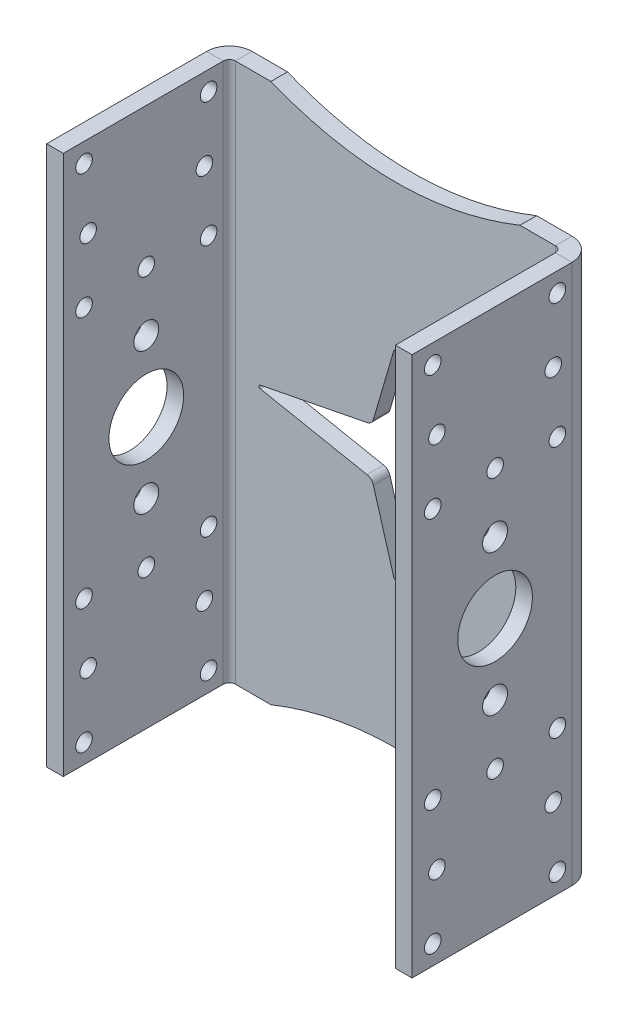
SolidWorks part; units mm, degrees
note: The reader was unsure of these and kept them because the rebuilt part matched: flange length of "边线-法兰1", "边线-法兰2".
ref_plane "前视基准面" through (0, 0, 0) normal (0, 0, 1) x (1, 0, 0)
ref_plane "上视基准面" through (0, 0, 0) normal (0, 1, 0) x (1, 0, 0)
ref_plane "右视基准面" through (0, 0, 0) normal (1, 0, 0) x (0, 0, -1)
sketch "草图1" plane through (0, 0, 0) normal (0, 0, 1) x (1, 0, 0)
  line L1 (-24.9105, 29.2763) -> (19.0895, 29.2763)
  line L2 (-24.9105, 29.2763) -> (-24.9105, -35.7237)
  line L3 (-24.9105, -35.7237) -> (19.0895, -35.7237)
  line L4 (19.0895, 29.2763) -> (19.0895, -35.7237)
  dimension "D1" = 44
  dimension "D2" = 65
base flange "基体-法兰1" sketch "草图1" thickness 2 reverse thickness direction no parameters "D1"=0.7366
edge flange "边线-法兰1" sketch "草图8" flange angle 90 flange length 22 flange position material inside bend radius 0.7366 thickness 2 relief rectangular parameters "D6"=10
sketch "草图8" plane through (-24.9105, 0, 0) normal (-1, 0, 0) x (0, -1, 0)
  line L0 (-29.2763, 0) -> (35.7237, 0) construction
  line L1 (-29.2763, 0) -> (35.7237, 0)
  line L2 (-29.2763, 0) -> (-29.2763, 20)
  line L3 (-29.2763, 20) -> (35.7237, 20)
  line L4 (35.7237, 20) -> (35.7237, 0)
bend "边线折弯1" bend radius 0.7366 bend angle 90 parameters "D5"=1
edge flange "边线-法兰2" sketch "草图11" flange angle 90 flange length 22 flange position material inside bend radius 0.7366 thickness 2 relief rectangular parameters "D6"=10
sketch "草图11" plane through (19.0895, 0, 0) normal (1, 0, 0) x (0, 1, 0)
  line L0 (-35.7237, 0) -> (29.2763, 0) construction
  line L1 (-35.7237, 0) -> (29.2763, 0)
  line L2 (-35.7237, 0) -> (-35.7237, 20)
  line L3 (-35.7237, 20) -> (29.2763, 20)
  line L4 (29.2763, 20) -> (29.2763, 0)
bend "边线折弯2" bend radius 0.7366 bend angle 90 parameters "D5"=2
sketch "草图12" plane through (0, 0, -2) normal (0, 0, -1) x (-1, 0, 0)
  line L16 (-14.3529, -3.2237) -> (0.0821, -0.3953)
  line L17 (2.9105, 9.2763) -> (5.7389, -0.3953)
  line L18 (5.7389, -0.3953) -> (20.1739, -3.2237)
  line L19 (20.1739, -3.2237) -> (5.7389, -6.0522)
  line L20 (5.7389, -6.0522) -> (2.9105, -15.7237)
  line L21 (2.9105, -15.7237) -> (0.0821, -6.0522)
  line L22 (0.0821, -6.0522) -> (-14.3529, -3.2237)
  line L23 (0.0821, -0.3953) -> (2.9105, 9.2763)
extrude "切除-拉伸1" cut sketch "草图12" against normal blind 2 normal cut yes
sketch "草图13" plane through (0, 0, -2) normal (0, 0, -1) x (-1, 0, 0)
  line L0 (2.9105, 29.2763) -> (17.9105, 29.2763)
  line L1 (-16.3529, 29.2763) -> (22.1739, 29.2763) construction
  line L5 (-12.0895, 29.2763) -> (2.9105, 29.2763)
  spline S0 degree 2 poles (-12.0895, 29.2763) (2.9105, 23.2763) (17.9105, 29.2763) knots 0 0 0 1 1 1
extrude "切除-拉伸2" cut sketch "草图13" against normal blind 2 normal cut yes
sketch "草图14" plane through (0, 0, -2) normal (0, 0, -1) x (-1, 0, 0)
  line L0 (2.9105, -35.7237) -> (17.9105, -35.7237)
  line L1 (24.9105, -35.7237) -> (-19.0895, -35.7237) construction
  line L5 (22.1739, -35.7237) -> (-16.3529, -35.7237) construction
  line L6 (-12.0895, -35.7237) -> (2.9105, -35.7237)
  spline S0 degree 2 poles (-12.0895, -35.7237) (2.9105, -29.7237) (17.9105, -35.7237) knots 0 0 0 1 1 1
extrude "切除-拉伸3" cut sketch "草图14" against normal blind 2 normal cut yes
sketch "草图16" plane through (19.0895, 0, 0) normal (1, 0, 0) x (0, 0, -1)
  circle A4 centre (-17.5, 26.9559) radius 1
  circle A5 centre (-2.5, 26.9559) radius 1
  circle A6 centre (-2.5, 11.9559) radius 1
  circle A7 centre (-17.5, 11.9559) radius 1
  circle A9 centre (-3, 19.4559) radius 1
  circle A10 centre (-17, 19.4559) radius 1
  circle A11 centre (-10, 12.4559) radius 1
  circle A12 centre (-10, -18.9034) radius 1
  circle A13 centre (-17, -25.9034) radius 1
  circle A14 centre (-3, -25.9034) radius 1
  circle A15 centre (-17.5, -18.4034) radius 1
  circle A16 centre (-2.5, -18.4034) radius 1
  circle A17 centre (-2.5, -33.4034) radius 1
  circle A18 centre (-17.5, -33.4034) radius 1
  circle A19 centre (-10, -3.2237) radius 4.5
  circle A20 centre (-10, 5.2763) radius 1.5
  circle A21 centre (-10, -11.7237) radius 1.5
extrude "切除-拉伸5" cut sketch "草图16" against normal blind 50 normal cut yes
fillet "圆角2" radius 0.2 1 edges at (-2.9105, 9.2763, -1)
fillet "圆角3" radius 0.2 1 edges at (-20.1739, -3.2237, -1)
fillet "圆角4" radius 0.2 1 edges at (-2.9105, -15.7237, -1)
fillet "圆角5" radius 0.2 1 edges at (14.3529, -3.2237, -1)
fillet "圆角7" radius 1 4 edges at (-5.7389, -6.0522, -1) (-5.7389, -0.3953, -1) (-0.0821, -6.0522, -1) (-0.0821, -0.3953, -1)
sketch "折弯-线1" plane through (0, 0, 0) normal (0, 1, 0) x (1, 0, 0)
sketch "边界框1" plane through (0, 0, 0) normal (0, 1, 0) x (1, 0, 0)
sheet metal parameters "钣金6" thickness 2 parameters "D1"=0.7366
flat pattern "平板型式6" [suppressed]
sketch "折弯-线2" plane through (0, 0, 0) normal (0, 1, 0) x (1, 0, 0)
sketch "边界框2" [suppressed] plane through (0, 0, 0) normal (0, 1, 0) x (1, 0, 0)
sheet metal parameters "钣金7" thickness 2 parameters "D1"=0.7366
flat pattern "平板型式6" [suppressed]
sketch "折弯-线2" plane through (0, 0, 0) normal (0, 1, 0) x (1, 0, 0)
sketch "边界框2" [suppressed] plane through (0, 0, 0) normal (0, 1, 0) x (1, 0, 0)
bend of the flat pattern "展平-<边线折弯1>1"
sheet metal parameters "钣金8" thickness 2 parameters "D1"=0.7366
flat pattern "平板型式6" [suppressed]
sketch "折弯-线2" plane through (0, 0, 0) normal (0, 1, 0) x (1, 0, 0)
sketch "边界框2" [suppressed] plane through (0, 0, 0) normal (0, 1, 0) x (1, 0, 0)
bend of the flat pattern "展平-<边线折弯1>1"
bend of the flat pattern "展平-<边线折弯2>1"
sheet metal parameters "钣金9" thickness 2 parameters "D1"=0.7366
flat pattern "平板型式6" [suppressed]
sketch "折弯-线2" plane through (0, 0, 0) normal (0, 1, 0) x (1, 0, 0)
sketch "边界框2" [suppressed] plane through (0, 0, 0) normal (0, 1, 0) x (1, 0, 0)
bend of the flat pattern "展平-<边线折弯1>1"
bend of the flat pattern "展平-<边线折弯2>1"
sheet metal parameters "钣金10" thickness 2 parameters "D1"=0.7366
flat pattern "平板型式6" [suppressed]
sketch "折弯-线2" plane through (0, 0, 0) normal (0, 1, 0) x (1, 0, 0)
sketch "边界框2" [suppressed] plane through (0, 0, 0) normal (0, 1, 0) x (1, 0, 0)
bend of the flat pattern "展平-<边线折弯1>1"
bend of the flat pattern "展平-<边线折弯2>1"
sheet metal parameters "钣金11" thickness 2 parameters "D1"=0.7366
flat pattern "平板型式6" [suppressed]
sketch "折弯-线2" plane through (0, 0, 0) normal (0, 1, 0) x (1, 0, 0)
sketch "边界框2" [suppressed] plane through (0, 0, 0) normal (0, 1, 0) x (1, 0, 0)
bend of the flat pattern "展平-<边线折弯1>1"
bend of the flat pattern "展平-<边线折弯2>1"
sheet metal parameters "钣金13" thickness 2 parameters "D1"=0.7366
flat pattern "平板型式6" [suppressed]
sketch "折弯-线2" plane through (0, 0, 0) normal (0, 1, 0) x (1, 0, 0)
sketch "边界框2" [suppressed] plane through (0, 0, 0) normal (0, 1, 0) x (1, 0, 0)
bend of the flat pattern "展平-<边线折弯1>1"
bend of the flat pattern "展平-<边线折弯2>1"
